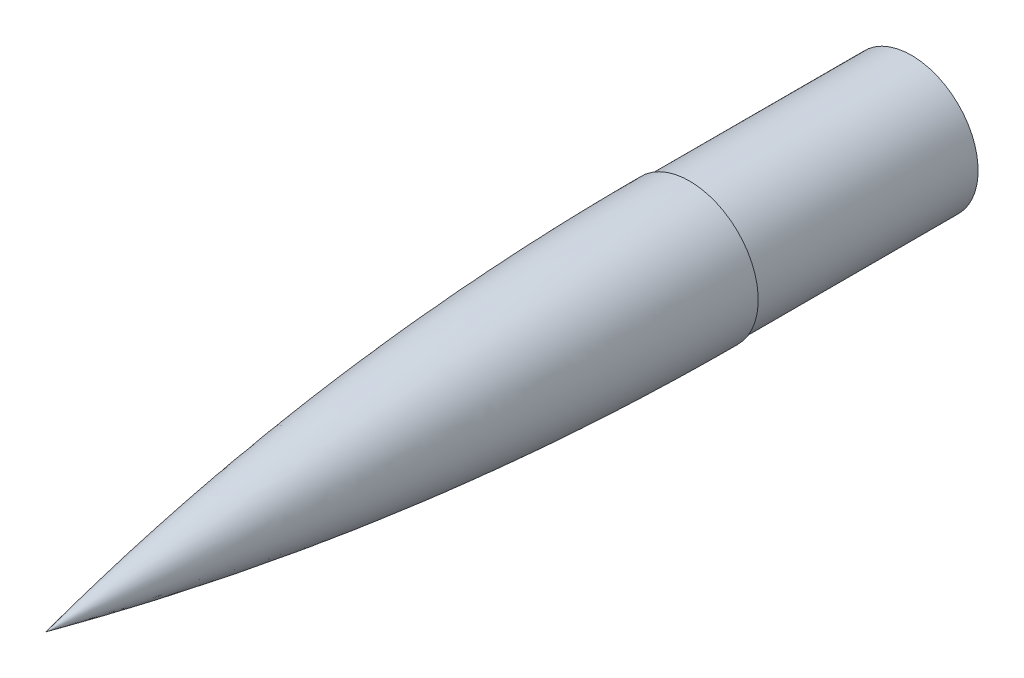
SolidWorks part; units mm, degrees
ref_plane "Front Plane" through (0, 0, 0) normal (0, 0, 1) x (1, 0, 0)
ref_plane "Top Plane" through (0, 0, 0) normal (0, 1, 0) x (1, 0, 0)
ref_plane "Right Plane" through (0, 0, 0) normal (1, 0, 0) x (0, 0, -1)
sketch "Sketch2" plane through (0, 0, 0) normal (1, 0, 0) x (0, 0, -1)
  line L0 (0, 1708.0816) -> (0, 1747.3373)
  line L1 (0, 1708.0816) -> (-368.3, 1708.0816)
  arc A0 (0, 1747.3373) -> (-368.3, 1708.0816) centre (0, 0) ccw
  arc A1 (-368.3, 1708.0816) -> (0, 1747.3373) centre (0, 0) ccw construction
  dimension "D1" = 39.2557
  dimension "D2" = 368.3
revolve "Revolve1" add sketch "Sketch2" angle 360 about L1
shell "Shell1" thickness 1.1557 removed face at (-39.2557, 1708.0816, 0)
sketch "Sketch3" plane through (0, 0, 0) normal (0, 0, -1) x (-1, 0, 0)
  circle A0 centre (0, 1708.0816) radius 38.1 construction
  circle A1 centre (0, 1708.0816) radius 38.1
  circle A2 centre (0, 1708.0816) radius 36.5125
  dimension "D1" = 73.025
extrude "Boss-Extrude1" add sketch "Sketch3" along normal blind 127 and the other way up to surface
equation "\"AIRFRAME_OD\"= 3.091in"
equation "\"AIRFRAME_ID\"= 3.00in"
equation "\"FLAT_T\"= 0.125in"
equation "\"NOSE_EXP_L\"= 3.5in"
equation "\"NOSE_SHOULDER_L\"= 5in"
equation "\"MAIN_L\"= 30in"
equation "\"RECO_COUP_L\"= 6in"
equation "\"RECO_SWITCH_L\"= 1.5in"
equation "\"DROGUE_L\"= 14in"
equation "\"ATS_FORE_COUP_L\"= 4in"
equation "\"ATS_AFT_COUP_L\"= 2.5in"
equation "\"LOWER_L\"= 16in"
equation "\"FIN_N\"= 4"
equation "\"CR_AFT_X\"= 0.5in"
equation "\"CR_FORE_X\"= 6in"
equation "\"D1@Sketch2\"=\"AIRFRAME_OD\"/2"
equation "\"COUPLER_OD\"= 2.998in"
equation "\"COUPLER_ID\"= 2.875in"
equation "\"RECO_ROD_X\"= 1.5in"
equation "\"ATS_ROD_X\"= 2in"
equation "\"FIN_ROOT\"= 5in"
equation "\"FIN_X\"= 0.75in"
equation "\"MOTOR_OD\"= 2.25in"
equation "\"MOTOR_ID\"= 2.126in"
equation "\"MOTOR_L\"= 8in"
equation "\"MOTOR_LOWER_X\"= 0.5in"
equation "\"NOSE_CONE_L\"=14.5in"
equation "\"D2@Sketch2\"=\"NOSE_CONE_L\""
equation "\"D1@Shell1\"=(\"AIRFRAME_OD\"-\"AIRFRAME_ID\")/2"
equation "\"D1@Sketch3\"=\"COUPLER_ID\""
equation "\"D1@Boss-Extrude1\"=\"NOSE_SHOULDER_L\""
